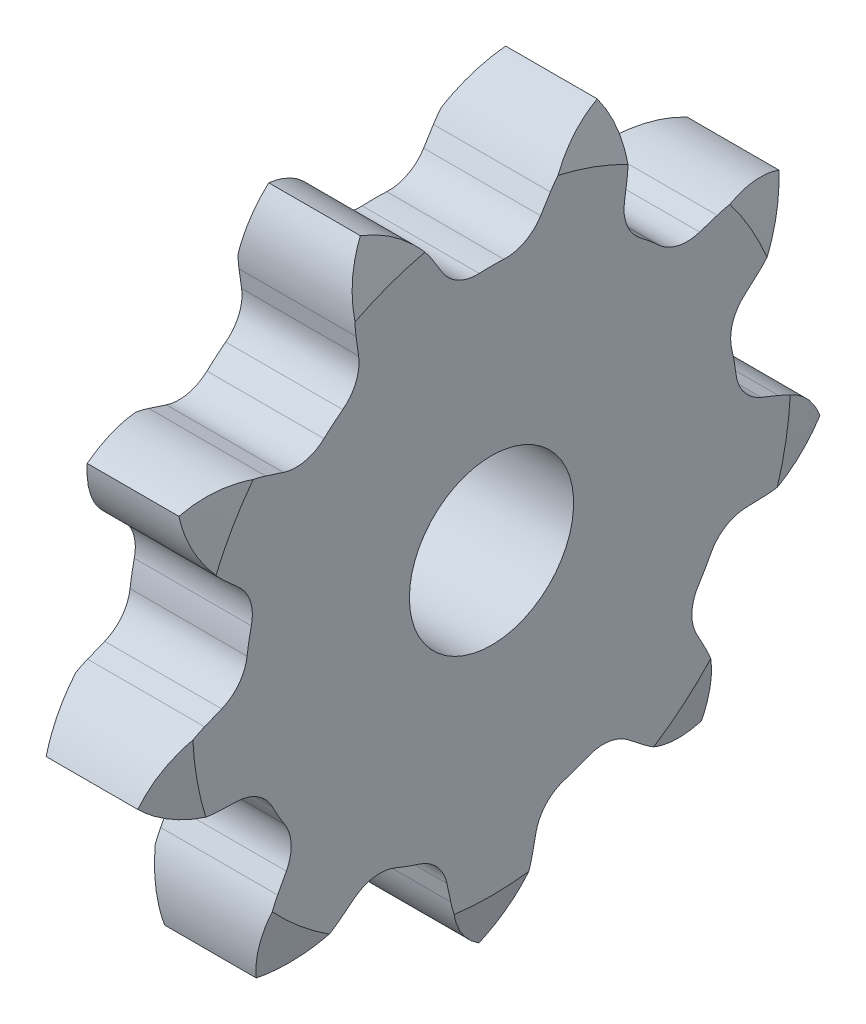
SolidWorks part; units mm, degrees
ref_plane "Plane1" through (0, 0, 0) normal (0, 0, 1) x (1, 0, 0)
ref_plane "Plane2" through (0, 0, 0) normal (0, 1, 0) x (1, 0, 0)
ref_plane "Plane3" through (0, 0, 0) normal (1, 0, 0) x (0, 0, -1)
sketch "Clipboard" plane through (0, 0, 0) normal (0, 1, 0) x (1, 0, 0)
  line L0 (0, 0) -> (62.7182, -9.9336)
  line L1 (-15, 0) -> (100, 0) construction
  line L2 (0, 0) -> (-2.1039, 2.3779)
  line L3 (0, 0) -> (-11.863, 4.5341)
  line L4 (0, 0) -> (8.5297, 1.351)
  line L5 (0, 0) -> (-71.3958, -26.6285)
  line L6 (0, 0) -> (-30.0043, -20.244)
  line L7 (-2.1039, 2.3779) -> (14.2981, 76.7917)
  line L8 (-76.2, 54.61) -> (-19.7358, 54.61)
  line L9 (-66.6514, 23.5599) -> (-51.1233, 26.8605)
  line L10 (-76.2, 71.12) -> (16.6308, 71.12)
  line L11 (0, 0) -> (-38.1, 0)
  line L12 (-76.2, 101.6) -> (-31.75, 101.6)
  circle A0 centre (0, 0) radius 15.875
  circle A1 centre (0, 0) radius 25.4
  circle A2 centre (0, 0) radius 25.4
  dimension "Num_teeth" = 9
  dimension "Pitch_radius" = 92.8308
  dimension "Width" = 38.1
  dimension "F" = 44.45
  dimension "H" = 15.875
  dimension "Thickness" = 36.195
sketch "BasProSke" plane through (0, 0, 0) normal (0, 1, 0) x (1, 0, 0)
  line L0 (-10, 0) -> (60, 0) construction
  line L1 (0, 0) -> (0, 92.496)
  line L2 (0, 0) -> (36.195, 0)
  line L3 (36.195, 0) -> (36.195, 92.496)
  line L4 (31.8516, 108.7058) -> (4.3434, 108.7058)
  line L5 (0, 92.496) -> (4.3434, 108.7058)
  line L6 (36.195, 92.496) -> (31.8516, 108.7058)
  dimension "Thickness" = 36.195
  dimension "Diameter" = 217.4116
  dimension "D1" = 15
  dimension "D2" = 15
revolve "Base-Revolve" add sketch "BasProSke" angle 360 about L0
sketch "TooCutSke" plane through (0, 0, 0) normal (1, 0, 0) x (0, 0, -1)
  line L0 (-15.1941, 82.0537) -> (-18.2226, 86.9003)
  line L1 (0, 0) -> (0, 107) construction
  line L2 (3.175, 0) -> (3.175, 119.782) construction
  line L3 (15.1941, 82.0537) -> (18.2226, 86.9003)
  line L4 (36.6386, 100.6637) -> (40.9823, 112.5978)
  line L5 (3.175, 96.303) -> (55.3039, 63.7293) construction
  line L6 (-36.6386, 100.6637) -> (-40.9823, 112.5978)
  arc A0 (3.7919, 76.0994) -> (-3.7919, 76.0994) centre (0, 0) ccw
  arc A1 (3.7919, 76.0994) -> (15.1941, 82.0537) centre (4.4239, 88.7836) ccw
  arc A2 (-3.7919, 76.0994) -> (-15.1941, 82.0537) centre (-4.4239, 88.7836) cw
  circle A3 centre (0, 0) radius 92.8308 construction
  circle A4 centre (3.175, 92.7765) radius 15.875 construction
  arc A5 (18.2226, 86.9003) -> (36.6386, 100.6637) centre (45.1481, 70.0753) cw
  arc A6 (-18.2226, 86.9003) -> (-36.6386, 100.6637) centre (-45.1481, 70.0753) ccw
  arc A7 (40.9823, 112.5978) -> (-40.9823, 112.5978) centre (0, 0) ccw
  dimension "Pitch_radius" = 92.8308
  dimension "R" = 12.7
  dimension "Dr" = 76.1938
  dimension "H" = 15.875
  dimension "Ag" = 64
  dimension "Angle" = 40
extrude "ToothCut" cut sketch "TooCutSke" along normal through all
pattern_circular "TeethCuts" count 9 every 40 about axis through (-10, 0, 0) along (1, 0, 0) of "ToothCut"
sketch "HubNeaOneSke" plane through (0, 0, 0) normal (-1, 0, 0) x (0, 0, 1)
  circle A0 centre (0, 0) radius 25.4
  dimension "Diameter" = 50.8
extrude "HubNearOne" [suppressed] add sketch "HubNeaOneSke" along normal blind 40.0051
sketch "HubNeaBotSke" plane through (0, 0, 0) normal (-1, 0, 0) x (0, 0, 1)
  circle A0 centre (0, 0) radius 25.4
  dimension "Diameter" = 50.8
extrude "HubNearBoth" [suppressed] add sketch "HubNeaBotSke" along normal blind 20.0025
ref_plane "FarPln" through (36.195, 0, 0) normal (1, 0, 0) x (0, 0, -1)
sketch "HubFarSke" plane through (36.195, 0, 0) normal (1, 0, 0) x (0, 0, -1)
  circle A0 centre (0, 0) radius 25.4
  dimension "Diameter" = 50.8
extrude "HubFar" [suppressed] add sketch "HubFarSke" along normal blind 20.0025
sketch "BorSke" plane through (0, 0, 0) normal (1, 0, 0) x (0, 0, -1)
  circle A0 centre (0, 0) radius 25.4
  dimension "Diameter" = 50.8
extrude "Bore" cut sketch "BorSke" along normal mid plane 152.4001
sketch "KeySke" plane through (0, 0, 0) normal (1, 0, 0) x (0, 0, -1)
  line L0 (-6.35, 0) -> (-6.35, 31.0642)
  line L1 (-6.35, 31.0642) -> (6.35, 31.0642)
  line L2 (6.35, 31.0642) -> (6.35, 0)
  line L3 (0, 0) -> (0, 34) construction
  line L4 (-6.35, 0) -> (6.35, 0)
  dimension "Width" = 12.7
extrude "Keyway" [suppressed] cut sketch "KeySke" along normal mid plane 152.4001
pattern_circular "Keyway2" [suppressed] count 2 every 90 about axis through (-10, 0, 0) along (1, 0, 0) reverse direction yes
equation "\"Thickness@Clipboard\" = \"Width@Clipboard\" * 0.95"
equation "\"H@Clipboard\" = \"Diameter@Clipboard\" / 2.0"
equation "\"OAL@Clipboard\" = \"Thickness@Clipboard\""
equation "\"Pitch_radius@Clipboard\" = ( \"Pitch@Clipboard\" / 2.0) / sin(3.14159265 / \"Num_teeth@Clipboard\" )"
equation "\"MHD@Clipboard\" = (1.0 / tan(3.14159265 / \"Num_teeth@Clipboard\" ) - 0.05) * \"Pitch@Clipboard\" - \"F@Clipboard\""
equation "\"MHD@Clipboard\" = ((sgn( \"MHD@Clipboard\" - \"Hub_dia@Clipboard\" )-1)*( \"MHD@Clipboard\" - \"Hub_dia@Clipboard\" ))/-2+ \"Hub_dia@Clipboard\""
equation "\"OAL@Clipboard\" = ((sgn( \"OAL@Clipboard\" - \"Overall_len@Clipboard\" )+1)*( \"OAL@Clipboard\" - \"Overall_len@Clipboard\" ))/2 + \"Overall_len@Clipboard\" + 0.000002"
equation "\"Num_teeth@TeethCuts\" = int( \"Show_teeth@Clipboard\" ) + 1"
equation "\"Num_teeth@TeethCuts\" = ((sgn( \"Num_teeth@TeethCuts\" - \"Num_teeth@Clipboard\" )-1)*( \"Num_teeth@TeethCuts\" - \"Num_teeth@Clipboard\" ))/-2+ \"Num_teeth@Clipboard\""
equation "\"Num_teeth@TeethCuts\" = ((sgn( \"Num_teeth@TeethCuts\" - 2.0)+1)*( \"Num_teeth@TeethCuts\" - 2.0))/2 +2.0"
equation "\"Angle@TeethCuts\" = 360.0 / \"Num_teeth@Clipboard\""
equation "\"Pitch_radius@TooCutSke\" = \"Pitch_radius@Clipboard\""
equation "\"Cp@TooCutSke\" = 0.05 * \"Pitch@Clipboard\""
equation "\"Rt@TooCutSke\" = 0.5 * \"Pitch@Clipboard\""
equation "\"R@TooCutSke\"  = 0.8 * \"H@Clipboard\""
equation "\"Dr@TooCutSke\" = \"Pitch_radius@Clipboard\" - \"H@Clipboard\" - 0.03"
equation "\"Ag@TooCutSke\" =  2.0 * \"Ap@Clipboard\" + 360.0 / \"Num_teeth@Clipboard\""
equation "\"H@TooCutSke\" = \"H@Clipboard\""
equation "\"Angle@TooCutSke\" =  360.0 / \"Num_teeth@Clipboard\""
equation "\"Wf@TooCutSke\" = 0.01 * \"Pitch@Clipboard\" * \"Num_teeth@Clipboard\""
equation "\"Wf@TooCutSke\" = ((sgn( \"Wf@TooCutSke\" - \"H@Clipboard\" * 0.8 )-1)*( \"Wf@TooCutSke\" - \"H@Clipboard\" * 0.8 ))/-2+ \"H@Clipboard\" * 0.8"
equation "\"Diameter@BasProSke\" = 2.0 * \"Pitch_radius@Clipboard\"  + 2.0 * \"H@Clipboard\""
equation "\"Thickness@BasProSke\"  = \"Thickness@Clipboard\""
equation "\"G1@BasProSke\" =  \"Thickness@Clipboard\" * 0.12"
equation "\"G2@BasProSke\" =   \"Thickness@Clipboard\" * 0.12"
equation "\"Diameter@HubNeaOneSke\" = \"MHD@Clipboard\""
equation "\"Length@HubNearOne\" = \"OAL@Clipboard\" - \"Thickness@BasProSke\""
equation "\"Diameter@HubNeaBotSke\" = \"MHD@Clipboard\""
equation "\"Length@HubNearBoth\" = ( \"OAL@Clipboard\" - \"Thickness@BasProSke\" ) / 2.0"
equation "\"Thickness@FarPln\" = \"Thickness@BasProSke\""
equation "\"Diameter@HubFarSke\" = \"MHD@Clipboard\""
equation "\"Length@HubFar\" = ( \"OAL@Clipboard\" - \"Thickness@BasProSke\" ) / 2.0"
equation "\"D1@Bore\" = \"OAL@Clipboard\" * 2.0"
equation "\"D1@Keyway\" = \"OAL@Clipboard\" * 2.0"
equation "\"Offset@KeySke\" = \"T_dim@Clipboard\" - \"Diameter@BorSke\" / 2.0"
